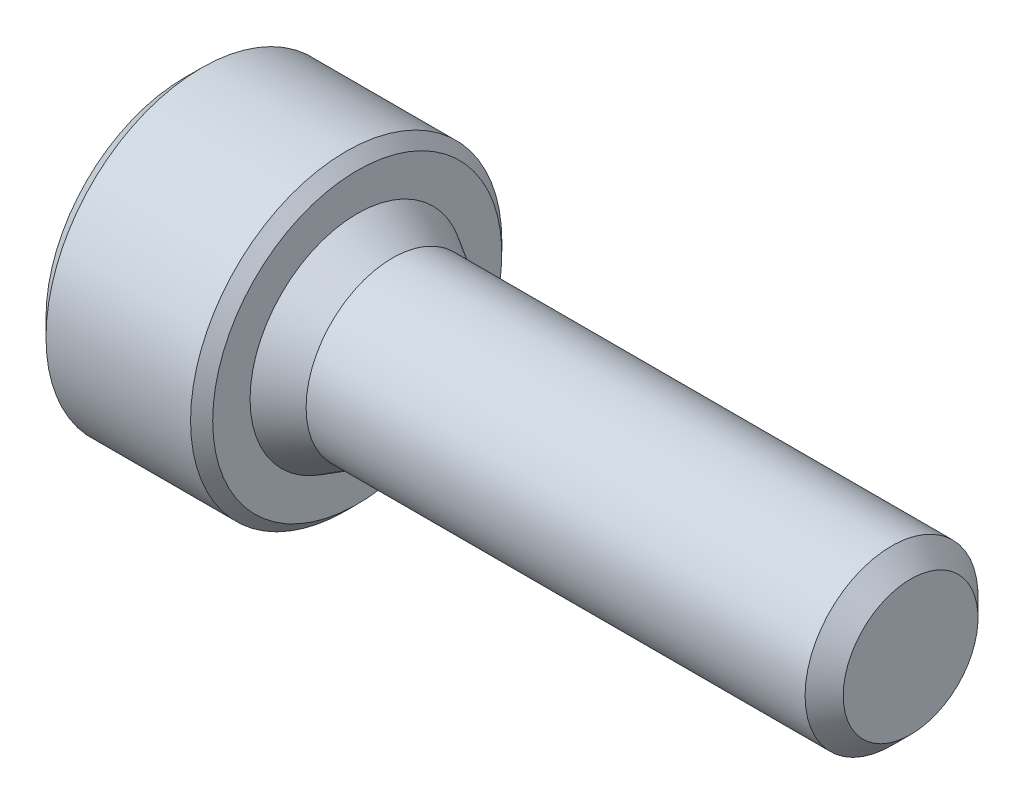
SolidWorks part; units mm, degrees
ref_plane "Front Plane" through (0, 0, 0) normal (0, 0, 1) x (1, 0, 0)
ref_plane "Top Plane" through (0, 0, 0) normal (0, 1, 0) x (1, 0, 0)
ref_plane "Right Plane" through (0, 0, 0) normal (1, 0, 0) x (0, 0, -1)
sketch "Sketch1" plane through (0, 0, 0) normal (0, 0, 1) x (1, 0, 0)
  line L0 (-2.5, 0) -> (-2.5, 2.25)
  line L1 (-2.5, 2.25) -> (0, 2.25)
  line L2 (0, 2.25) -> (0, 1.55)
  line L3 (0, 1.55) -> (0.51, 1.25)
  line L4 (0.51, 1.25) -> (7.724, 1.25)
  line L5 (7.724, 1.25) -> (8, 0.974)
  line L6 (8, 0.974) -> (8, 0)
  line L7 (8, 0) -> (-2.5, 0)
  line L8 (8, 0) -> (-2.5, 0) construction
revolve "Revolve1" add sketch "Sketch1" angle 360 about L8 reverse direction yes
cosmetic thread "Cosmetic Thread1" parameters "D1"=6.65, "D2"=1.948
sketch "Sketch2" plane through (0, 0, 0) normal (0, 0, 1) x (1, 0, 0)
  line L0 (-2.5, 2.7) -> (-2.5, 2)
  line L1 (-2.5, 2) -> (-2.25, 2.25)
  line L2 (-2.25, 2.25) -> (-0.16, 2.25)
  line L3 (-0.16, 2.25) -> (0, 2.09)
  line L4 (0, 2.09) -> (0, 2.7)
  line L5 (0, 2.7) -> (-2.5, 2.7)
  line L6 (0, 0) -> (-2.5, 0) construction
revolve "Cut-Revolve1" cut sketch "Sketch2" angle 360 about L6 reverse direction yes
sketch "Sketch3" plane through (0, 0, 0) normal (0, 0, 1) x (1, 0, 0)
  line L0 (-2.5, 0) -> (-2.5, 1.14)
  line L1 (-2.5, 1.14) -> (-2.36, 1)
  line L2 (-2.36, 1) -> (-1.4, 1)
  line L3 (-1.4, 1) -> (-0.8226, 0)
  line L4 (-0.8226, 0) -> (-2.5, 0)
  line L5 (-0.8226, 0) -> (-2.5, 0) construction
revolve "Cut-Revolve2" cut sketch "Sketch3" angle 360 about L5 reverse direction yes
ref_plane "Plane1" through (-2.5, 0, 0) normal (1, 0, 0) x (0, 0, -1)
sketch "Sketch4" plane through (-2.5, 0, 0) normal (1, 0, 0) x (0, 0, -1)
  line L0 (-1, -0.5774) -> (0, -1.1547)
  line L1 (0, -1.1547) -> (1, -0.5774)
  line L2 (1, -0.5774) -> (1, 0.5774)
  line L3 (1, 0.5774) -> (0, 1.1547)
  line L4 (0, 1.1547) -> (-1, 0.5774)
  line L5 (-1, 0.5774) -> (-1, -0.5774)
extrude "Cut-Extrude1" cut sketch "Sketch4" along normal blind 1.1 and the other way blind 1.1
ref_plane "Plane2" through (-2.5, 0, 0) normal (1, 0, 0) x (0, 0, -1)
ref_plane "Plane3" through (8, 0, 0) normal (1, 0, 0) x (0, 0, -1)
ref_plane "Plane4" through (0, 0, 0) normal (1, 0, 0) x (0, 0, -1)
ref_plane "ANBAU XY" through (0, 0, 0) normal (-1, 0, 0) x (0, 0, 1)
ref_plane "ANBAU XZ" through (0, 0, 0) normal (0, 1, 0) x (1, 0, 0)
ref_plane "ANBAU YZ" through (0, 0, 0) normal (0, 0, -1) x (-1, 0, 0)
ref_axis "ANBAU X" through (0, 0, 80.9) along (0, 0, -1)
ref_axis "ANBAU Y" through (0, 50, 0) along (0, -1, 0)
ref_axis "ANBAU Z" through (-80.9, 0, 0) along (1, 0, 0)
sketch3d "ANBAU"
  point P0 (0, 0, 0)
ref_plane "IP1 XY" through (0, 0, 0) normal (1, 0, 0) x (0, 0, -1)
ref_plane "IP1 XZ" through (0, 0, 0) normal (0, -1, 0) x (-1, 0, 0)
ref_plane "IP1 YZ" through (0, 0, 0) normal (0, 0, -1) x (-1, 0, 0)
ref_axis "IP1 X" through (0, 0, 80.9) along (0, 0, -1)
ref_axis "IP1 Y" through (0, -50, 0) along (0, 1, 0)
ref_axis "IP1 Z" through (80.9, 0, 0) along (-1, 0, 0)
sketch3d "IP1"
  point P0 (0, 0, 0)
ref_plane "IP2 XY" through (-2.5, 0, 0) normal (1, 0, 0) x (0, 0, -1)
ref_plane "IP2 XZ" through (0, 0, 0) normal (0, -1, 0) x (-1, 0, 0)
ref_plane "IP2 YZ" through (0, 0, 0) normal (0, 0, -1) x (-1, 0, 0)
ref_axis "IP2 X" through (-2.5, 0, 80.9) along (0, 0, -1)
ref_axis "IP2 Y" through (-2.5, -50, 0) along (0, 1, 0)
ref_axis "IP2 Z" through (80.9, 0, 0) along (-1, 0, 0)
sketch3d "IP2"
  point P0 (-2.5, 0, 0)
ref_plane "IP3 XY" through (8, 0, 0) normal (1, 0, 0) x (0, 0, -1)
ref_plane "IP3 XZ" through (0, 0, 0) normal (0, -1, 0) x (-1, 0, 0)
ref_plane "IP3 YZ" through (0, 0, 0) normal (0, 0, -1) x (-1, 0, 0)
ref_axis "IP3 X" through (8, 0, 80.9) along (0, 0, -1)
ref_axis "IP3 Y" through (8, -50, 0) along (0, 1, 0)
ref_axis "IP3 Z" through (80.9, 0, 0) along (-1, 0, 0)
sketch3d "IP3"
  point P0 (8, 0, 0)
other "Freeze***"
